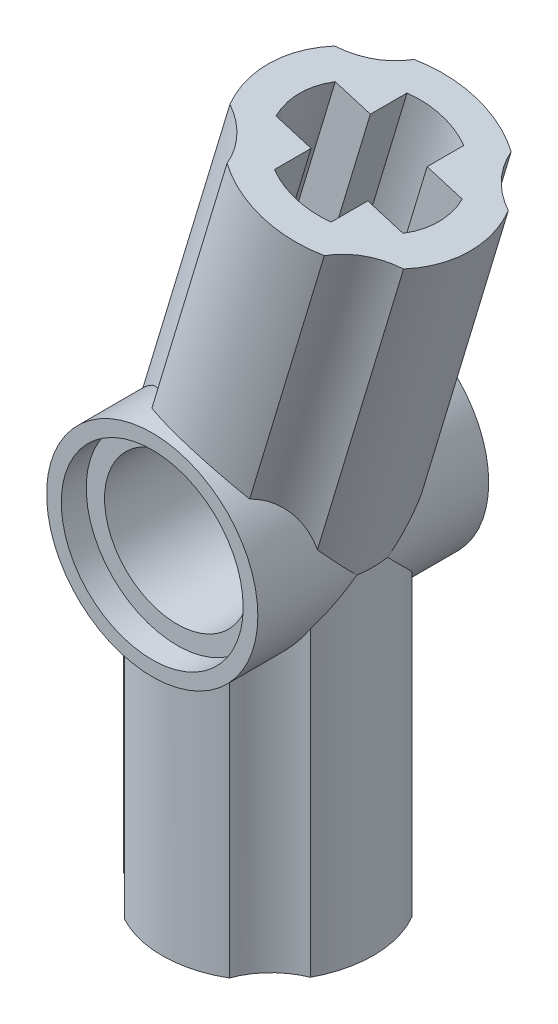
SolidWorks part; units mm, degrees
ref_plane "Front Plane" through (0, 0, 0) normal (0, 0, 1) x (1, 0, 0)
ref_plane "Top Plane" through (0, 0, 0) normal (0, 1, 0) x (1, 0, 0)
ref_plane "Right Plane" through (0, 0, 0) normal (1, 0, 0) x (0, 0, -1)
sketch "Croquis1" plane through (0, 0, 0) normal (0, 0, 1) x (1, 0, 0)
  circle A0 centre (0, 0) radius 3.1
  circle A1 centre (0, 0) radius 3.6
  circle A2 centre (0, 0) radius 2.475
  dimension "D1" = 4.95
  dimension "D2" = 6.2
  dimension "D3" = 7.2
extrude "Saliente-Extruir1" add sketch "Croquis1" along normal blind 7.87 contours A1 A0 region at (-3.4982, 0, 0)
extrude "Saliente-Extruir2" add sketch "Croquis1<3>" along normal offset from surface (6.17 mm away) 0.85 from offset 0.85 contours A0 A2 region at (-3.0123, 0, 0) up to face at (3.1, 0, 7.87)
sketch "Croquis1<3>" plane through (0, 0, 0) normal (0, 0, 1) x (1, 0, 0) same geometry as "Croquis1"
ref_plane "Plano1" through (0, -4, 0) normal (0, 1, 0) x (1, 0, 0)
sketch "Croquis2" plane through (0, -4, 0) normal (0, 1, 0) x (1, 0, 0)
  line L0 (-1.01, -6.1945) -> (-1.01, -4.945)
  line L1 (1.01, -6.1945) -> (1.01, -4.945)
  line L2 (-2.2595, -2.925) -> (-1.01, -2.925)
  line L3 (2.2595, -4.945) -> (1.01, -4.945)
  line L4 (-1.01, -4.945) -> (-2.2595, -4.945)
  line L5 (1.01, -2.925) -> (1.01, -1.6755)
  line L6 (-1.01, -2.925) -> (-1.01, -1.6755)
  line L7 (1.01, -2.925) -> (2.2595, -2.925)
  arc A0 (-1.01, -6.1945) -> (1.01, -6.1945) centre (0, -3.935) ccw
  arc A1 (-1.7125, -7.1016) -> (1.8067, -7.0488) centre (0, -3.935) ccw
  arc A2 (-1.7125, -7.1016) -> (-3.1138, -5.7417) centre (-3.94, -7.995) ccw
  arc A3 (-3.1666, -2.2225) -> (-1.8067, -0.8212) centre (-4.06, 0.005) ccw
  arc A4 (1.7125, -0.7684) -> (3.1138, -2.1283) centre (3.94, 0.125) ccw
  arc A5 (3.1666, -5.6475) -> (1.8067, -7.0488) centre (4.06, -7.875) ccw
  arc A6 (3.1666, -5.6475) -> (3.1138, -2.1283) centre (0, -3.935) ccw
  arc A7 (1.7125, -0.7684) -> (-1.8067, -0.8212) centre (0, -3.935) ccw
  arc A8 (-3.1666, -2.2225) -> (-3.1138, -5.7417) centre (0, -3.935) ccw
  arc A9 (2.2595, -4.945) -> (2.2595, -2.925) centre (0, -3.935) ccw
  arc A10 (1.01, -1.6755) -> (-1.01, -1.6755) centre (0, -3.935) ccw
  arc A11 (-2.2595, -2.925) -> (-2.2595, -4.945) centre (0, -3.935) ccw
  dimension "D2" = 4.95
  dimension "D3" = 7.2
  dimension "D4" = 4.8
  dimension "D1" = 3.935
  dimension "D5" = 3.94
  dimension "D6" = 4.06
  dimension "D8" = 2.02
  dimension "D9" = 1.01
  dimension "D10" = 2.02
  dimension "D11" = 1.01
  dimension "D7" = 4
extrude "Saliente-Extruir3" add sketch "Croquis2" along normal up to surface (0.8334 mm away) contours A3 A8 A2 A1 A5 A6 A4 A7 A11 L2 L6 A10 L5 L7 A9 L3 L1 A0 L0 L4 up to face at (3.6, 0, 7.87)
extrude "Saliente-Extruir4" add sketch "Croquis2<3>" against normal blind 8 contours A3 A8 A2 A1 A5 A6 A4 A7 A11 L2 L6 A10 L5 L7 A9 L3 L1 A0 L0 L4 region at (-2.1977, -4, 6.1996)
sketch "Croquis2<3>" plane through (0, -4, 0) normal (0, 1, 0) x (1, 0, 0) same geometry as "Croquis2"
sketch "Croquis5" plane through (0, 0, 0) normal (1, 0, 0) x (0, 0, -1)
  line L0 (0, 0) -> (-7.87, 0) construction
  line L1 (-7.87, 3.6) -> (-7.87, -3.6) construction
ref_plane "Plano3" through (0, 0, 0) normal (-0.2882, -0.9576, 0) x (0, 0, 1)
ref_plane "Plano4" through (1.1528, 3.8303, 0) normal (-0.2882, -0.9576, 0) x (0, 0, 1)
sketch "Croquis7" plane through (1.1528, 3.8303, 0) normal (-0.2882, -0.9576, 0) x (0, 0, 1)
  line L0 (2.925, -2.2595) -> (2.925, -1.01)
  line L1 (4.945, -2.2595) -> (4.945, -1.01)
  line L2 (1.6755, 1.01) -> (2.925, 1.01)
  line L3 (6.1945, -1.01) -> (4.945, -1.01)
  line L4 (2.925, -1.01) -> (1.6755, -1.01)
  line L5 (4.945, 1.01) -> (4.945, 2.2595)
  line L6 (2.925, 1.01) -> (2.925, 2.2595)
  line L7 (4.945, 1.01) -> (6.1945, 1.01)
  line L8 (7.87, -3.6) -> (7.87, 3.6) construction
  arc A0 (2.925, -2.2595) -> (4.945, -2.2595) centre (3.935, 0) ccw
  arc A1 (2.2225, -3.1666) -> (5.7417, -3.1138) centre (3.935, 0) ccw
  arc A2 (2.2225, -3.1666) -> (0.8212, -1.8067) centre (-0.005, -4.06) ccw
  arc A4 (5.6475, 3.1666) -> (7.0488, 1.8067) centre (7.875, 4.06) ccw
  arc A6 (7.1016, -1.7125) -> (7.0488, 1.8067) centre (3.935, 0) ccw
  arc A7 (5.6475, 3.1666) -> (2.1283, 3.1138) centre (3.935, 0) ccw
  arc A8 (0.7684, 1.7125) -> (0.8212, -1.8067) centre (3.935, 0) ccw
  arc A9 (6.1945, -1.01) -> (6.1945, 1.01) centre (3.935, 0) ccw
  arc A10 (4.945, 2.2595) -> (2.925, 2.2595) centre (3.935, 0) ccw
  arc A11 (1.6755, 1.01) -> (1.6755, -1.01) centre (3.935, 0) ccw
  arc A12 (7.1016, -1.7125) -> (5.7417, -3.1138) centre (7.995, -3.94) ccw
  arc A13 (2.2225, -3.1666) -> (0.8212, -1.8067) centre (-0.005, -4.06) ccw
  arc A14 (0.7684, 1.7125) -> (2.1283, 3.1138) centre (-0.125, 3.94) ccw
  dimension "D1" = 4.95
  dimension "D2" = 7.2
  dimension "D3" = 4.8
  dimension "D13" = 2.4
  dimension "D4" = 3.94
  dimension "D5" = 4.06
  dimension "D6" = 2.02
  dimension "D7" = 1.01
  dimension "D8" = 2.02
  dimension "D9" = 1.01
  dimension "D10" = 3.935
  dimension "D11" = 3.94
  dimension "D12" = 4.06
  dimension "D14" = 4
extrude "Saliente-Extruir5" add sketch "Croquis7" along normal up to surface (0.8334 mm away) contours A12 A1 A2 A8 A14 A7 A4 A6 up to face at (0, -2.0794, 3.935)
extrude "Saliente-Extruir6" add sketch "Croquis7<3>" against normal blind 8 contours A14 A8 A2 A1 A12 A6 A4 A7 A11 L2 L6 A10 L5 L7 A9 L3 L1 A0 L0 L4 region at (3.3213, 3.1776, 1.7373)
sketch "Croquis7<3>" plane through (1.1528, 3.8303, 0) normal (-0.2882, -0.9576, 0) x (0, 0, 1) same geometry as "Croquis7"
equation "\"D9@Croquis2\"=\"D8@Croquis2\"/2"
equation "\"D11@Croquis2\"=\"D10@Croquis2\"/2"
equation "\"angle\"= 163"
